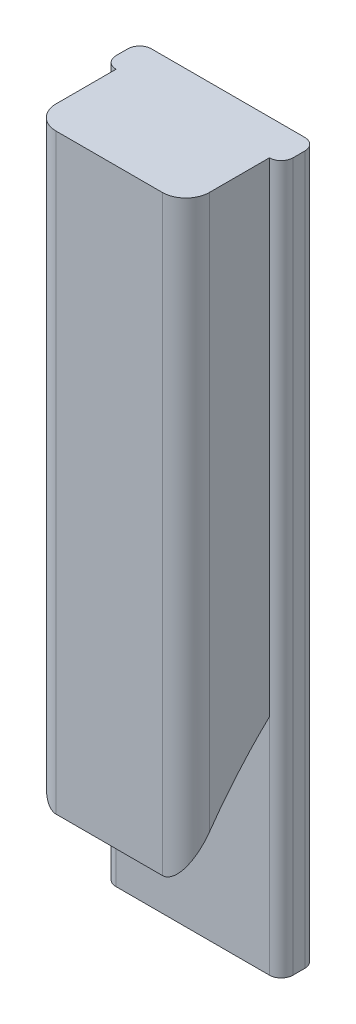
SolidWorks part; units mm, degrees
ref_plane "Front Plane" through (0, 0, 0) normal (0, 0, 1) x (1, 0, 0)
ref_plane "Top Plane" through (0, 0, 0) normal (0, 1, 0) x (1, 0, 0)
ref_plane "Right Plane" through (0, 0, 0) normal (1, 0, 0) x (0, 0, -1)
sketch "Sketch3" plane through (0, 0, 0) normal (0, 0, 1) x (1, 0, 0)
  line L1 (37.5, 150) -> (-37.5, 150)
  line L2 (37.5, 150) -> (37.5, -150)
  line L3 (37.5, -150) -> (-37.5, -150)
  line L4 (-37.5, 150) -> (-37.5, -150)
  line L5 (37.5, 150) -> (-37.5, -150) construction
  line L6 (37.5, -150) -> (-37.5, 150) construction
  point P0 (0, 0)
  dimension "D1" = 300
  dimension "D2" = 75
extrude "Boss-Extrude1" add sketch "Sketch3" along normal blind 15
sketch "Sketch4" plane through (0, 0, 0) normal (0, 0, -1) x (-1, 0, 0)
  line L0 (37.5, -150) -> (-37.5, -150) construction
  circle A0 centre (0, -120) radius 20
  dimension "D1" = 30
extrude "Cut-Extrude1" cut sketch "Sketch4" against normal blind 5
fillet "Fillet1" radius 5 4 edges at (-37.5, 0, 15) (37.5, 0, 15) (-37.5, 0, 0) (37.5, 0, 0)
ref_plane "Plane1" through (32.5, 150, 0) normal (0, -1, 0) x (-1, 0, 0)
sketch "Sketch6" plane through (0, 0, 0) normal (0, 0, -1) x (-1, 0, 0)
  line L1 (-32.5, 150) -> (32.5, 150) construction
  point P0 (0, 100)
  dimension "D1" = 50
ref_plane "Plane2" through (0, 0, 0) normal (0, 0, -1) x (-1, 0, 0)
ref_plane "Plane4" through (32.5, 0, 0) normal (1, 0, 0) x (0, 0, -1)
sketch "Sketch11" plane through (32.5, 0, 0) normal (1, 0, 0) x (0, 0, -1)
  line L0 (-15, 150) -> (-15, -55.1841)
  line L1 (-15, -150) -> (-15, 150) construction
  line L2 (-50.3957, -100.7031) -> (-50.3957, 150)
  line L3 (-50.3957, 150) -> (-15, 150)
  spline S0 degree 2 poles (-15, -55.1841) (-36.15, -75.2567) (-50.3957, -100.7031) knots 0 0 0 1 1 1
extrude "Boss-Extrude4" add sketch "Sketch11" against normal up to vertex (65 mm away) up to point (-32.5, -150, 15)
fillet "Fillet3" radius 10 1 edges at (-32.5, 24.6484, 50.3957) type face fillet first side face at (-32.5, 30.3383, 37.1223) second side face at (0, 24.6484, 50.3957)
fillet "Fillet4" radius 10 1 edges at (32.5, 24.6484, 50.3957) type face fillet first side face at (32.5, 30.3383, 37.1223) second side face at (5, 24.6484, 50.3957)
ref_plane "Plane5" through (0, 0, 10) normal (0, 0, -1) x (-1, 0, 0)
sketch "Sketch12" plane through (0, 0, 0) normal (0, 0, -1) x (-1, 0, 0)
  line L1 (23.394, -66.8431) -> (-26.606, -66.8431)
  line L2 (23.394, -66.8431) -> (23.394, -46.8431)
  line L3 (23.394, -46.8431) -> (-26.606, -46.8431)
  line L4 (-26.606, -66.8431) -> (-26.606, -46.8431)
  line L5 (23.394, -66.8431) -> (-26.606, -46.8431) construction
  line L6 (23.394, -46.8431) -> (-26.606, -66.8431) construction
  ellipse E0 centre (2.0845, -319.9891) end of major axis (5.0028, -599.9739) minor radius 120 construction
  point P0 (-1.606, -56.8431)
  dimension "D1" = 50
  dimension "D2" = 20
extrude "Boss-Extrude5" add sketch "Sketch12" along normal blind 4
fillet "Fillet5" radius 10 4 edges at (-23.394, -66.8431, -2) (-23.394, -46.8431, -2) (26.606, -66.8431, -2) (26.606, -46.8431, -2)
pattern_linear "LPattern3" count 7 spacing 25 along (0, 1, 0) of "Boss-Extrude5", "Fillet5"
